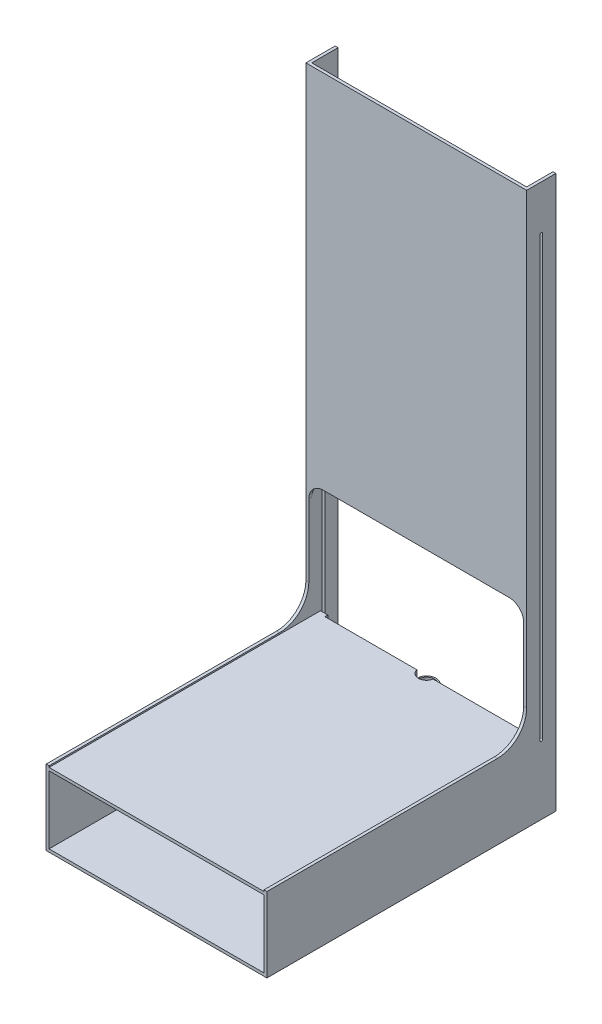
SolidWorks part; units mm, degrees
material "AISI 4340 Steel, annealed"
ref_plane "Front Plane" through (0, 0, 0) normal (0, 0, 1) x (1, 0, 0)
ref_plane "Top Plane" through (0, 0, 0) normal (0, 1, 0) x (1, 0, 0)
ref_plane "Right Plane" through (0, 0, 0) normal (1, 0, 0) x (0, 0, -1)
ref_plane "Right side of elevator platform" through (368, 0, 0) normal (1, 0, 0) x (0, 0, -1)
sketch "Sketch2" plane through (368, 0, 0) normal (1, 0, 0) x (0, 0, -1)
  line L0 (50, 236.5) -> (50, 1736.5) construction
  line L1 (45, 236.5) -> (45, 1736.5)
  line L2 (55, 236.5) -> (55, 1736.5)
  line L4 (0, 0) -> (100, 0)
  line L5 (0, 0) -> (0, 1800)
  line L6 (0, 1800) -> (100, 1800)
  line L7 (100, 0) -> (100, 1800)
  arc A0 (45, 236.5) -> (55, 236.5) centre (50, 236.5) ccw
  arc A1 (55, 1736.5) -> (45, 1736.5) centre (50, 1736.5) ccw
  point P2 (50, 986.5)
  dimension "D6" = 5
  dimension "D1" = 1800
  dimension "D2" = 100
  dimension "D3" = 50
  dimension "D4" = 236.5
  dimension "D5" = 63.5
extrude "Right side guide" add sketch "Sketch2" along normal blind 10
sketch "Sketch3" plane through (368, 0, 0) normal (-1, 0, 0) x (0, 0, 1)
  line L0 (0, 1800) -> (0, 0) construction
  line L1 (-100, 0) -> (0, 0)
  line L2 (-100, 0) -> (-100, 10)
  line L3 (-100, 10) -> (0, 10)
  line L4 (0, 0) -> (0, 10)
  dimension "D1" = 10
extrude "Bottom connection" add sketch "Sketch3" along normal blind 736
sketch "Sketch4" plane through (-368, 0, 0) normal (-1, 0, 0) x (0, 0, 1)
  line L0 (-55, 236.5) -> (-55, 1736.5) construction
  line L1 (-45, 1736.5) -> (-45, 236.5) construction
  line L2 (-55, 236.5) -> (-55, 1736.5)
  line L3 (-45, 1736.5) -> (-45, 236.5)
  line L4 (-100, 10) -> (0, 10)
  line L5 (0, 10) -> (0, 1800)
  line L6 (0, 1800) -> (-100, 1800)
  line L7 (-100, 1800) -> (-100, 10)
  line L9 (0, 10) -> (0, 1800)
  line L10 (0, 1800) -> (-100, 1800)
  line L11 (-100, 1800) -> (-100, 10)
  line L16 (-100, 10) -> (-100, 0)
  line L17 (-100, 0) -> (0, 0)
  line L18 (0, 0) -> (0, 10)
  line L19 (0, 10) -> (-100, 10)
  line L20 (-100, 10) -> (-100, 0)
  line L21 (-100, 0) -> (0, 0)
  line L22 (0, 0) -> (0, 10)
  arc A0 (-45, 1736.5) -> (-55, 1736.5) centre (-50, 1736.5) ccw construction
  arc A1 (-55, 236.5) -> (-45, 236.5) centre (-50, 236.5) ccw construction
  arc A2 (-45, 1736.5) -> (-55, 1736.5) centre (-50, 1736.5) ccw
  arc A3 (-55, 236.5) -> (-45, 236.5) centre (-50, 236.5) ccw
  dimension "D1" = 0
  dimension "D2" = 0
extrude "Left side guide" add sketch "Sketch4" along normal blind 10
sketch "Sketch5" plane through (0, 0, 0) normal (0, 0, 1) x (1, 0, 0)
  line L0 (-368, 10) -> (-368, 1800) construction
  line L1 (-368, 1800) -> (368, 1800)
  line L2 (-368, 1800) -> (-368, 653.8)
  line L3 (-368, 653.8) -> (368, 653.8)
  line L4 (368, 1800) -> (368, 653.8)
  line L5 (368, 1800) -> (368, 10) construction
  line L6 (378, 1800) -> (368, 1800) construction
  line L7 (-368, 10) -> (368, 10) construction
  dimension "D1" = 643.8
extrude "Structural webbing extrude" add sketch "Sketch5" against normal blind 10
sketch "Sketch6" plane through (0, 0, 0) normal (0, 0, 1) x (1, 0, 0)
  line L0 (-378, 251.5) -> (-378, 0)
  line L1 (-378, 0) -> (-378, 1800) construction
  line L2 (-378, 0) -> (378, 0)
  line L3 (378, 0) -> (378, 251.5)
  line L4 (378, 1800) -> (378, 0) construction
  line L5 (378, 251.5) -> (368, 251.5)
  line L6 (368, 653.8) -> (368, 10) construction
  line L7 (368, 251.5) -> (368, 10)
  line L8 (368, 10) -> (-368, 10)
  line L9 (-368, 10) -> (-368, 251.5)
  line L10 (-368, 10) -> (-368, 653.8) construction
  line L11 (-368, 251.5) -> (-378, 251.5)
  dimension "D1" = 241.5
extrude "Input roller holder extrude" add sketch "Sketch6" along normal blind 452.52
sketch "Sketch7" plane through (368, 0, 0) normal (-1, 0, 0) x (0, 0, 1)
  line L0 (0, 653.8) -> (0, 251.5) construction
  line L1 (452.52, 251.5) -> (-40, 251.5)
  line L2 (452.52, 251.5) -> (452.52, 241.5)
  line L3 (452.52, 241.5) -> (-40, 241.5)
  line L4 (-40, 251.5) -> (-40, 241.5)
  dimension "D1" = 40
  dimension "D2" = 10
extrude "Input roller platform" add sketch "Sketch7" along normal up to next
sketch "Sketch8" plane through (0, 251.5, 0) normal (0, 1, 0) x (1, 0, 0)
  line L1 (-378, -452.52) -> (-368, -452.52)
  line L2 (-378, -452.52) -> (-378, 0)
  line L3 (-378, 0) -> (-368, 0)
  line L4 (-368, -452.52) -> (-368, 0)
  line L5 (368, 0) -> (378, 0)
  line L6 (368, 0) -> (368, -452.52)
  line L7 (368, -452.52) -> (378, -452.52)
  line L8 (378, 0) -> (378, -452.52)
extrude "Siding outline" add sketch "Sketch8" along normal blind 5
sketch "Sketch9" plane through (0, 1800, 0) normal (0, 1, 0) x (1, 0, 0)
  line L8 (368, 100) -> (368, 10)
  line L9 (368, 10) -> (-368, 10)
  line L10 (-368, 10) -> (-368, 100)
  line L11 (-368, 100) -> (-378, 100)
  line L12 (-378, 100) -> (-378, 0)
  line L13 (-378, 0) -> (378, 0)
  line L14 (378, 0) -> (378, 100)
  line L15 (378, 100) -> (368, 100)
  line L16 (368, 100) -> (368, 10)
  line L17 (368, 10) -> (-368, 10)
  line L18 (-368, 10) -> (-368, 100)
  line L19 (-368, 100) -> (-378, 100)
  line L20 (-378, 100) -> (-378, 0)
  line L21 (-378, 0) -> (378, 0)
  line L22 (378, 0) -> (378, 100)
  line L23 (378, 100) -> (368, 100)
  dimension "D1" = 0
extrude "Lip to prevent box from falling out" add sketch "Sketch9" along normal blind 91.5
fillet "Vertical section fillets" radius 100 2 edges at (373, 256.5, 0) (-373, 256.5, 0)
fillet "Smaller fillets" radius 50 2 edges at (368, 653.8, -5) (-368, 653.8, -5)
sketch "Sketch11" plane through (0, 0, -40) normal (0, 0, -1) x (-1, 0, 0)
  line L0 (368, 251.5) -> (-368, 251.5) construction
  line L1 (-343, 251.5) -> (343, 251.5)
  line L2 (-343, 251.5) -> (-343, 241.5)
  line L3 (-343, 241.5) -> (343, 241.5)
  line L4 (343, 251.5) -> (343, 241.5)
  line L5 (368, 241.5) -> (-368, 241.5) construction
  line L6 (-368, 251.5) -> (-368, 241.5) construction
  line L7 (368, 251.5) -> (368, 241.5) construction
  dimension "D1" = 25
  dimension "D2" = 25
extrude "Gate spacing cut" cut sketch "Sketch11" against normal blind 10
sketch "Sketch12" plane through (-368, 0, 0) normal (1, 0, 0) x (0, 0, -1)
  line L1 (45, 221.5) -> (40, 221.5)
  line L2 (45, 221.5) -> (45, 10)
  line L3 (45, 10) -> (40, 10)
  line L4 (40, 221.5) -> (40, 10)
  line L5 (100, 1891.5) -> (100, 10) construction
  line L6 (45, 236.5) -> (45, 1736.5) construction
  line L7 (-452.52, 10) -> (100, 10) construction
  line L8 (40, 241.5) -> (-452.52, 241.5) construction
  line L9 (30, 241.5) -> (25, 241.5)
  line L10 (30, 241.5) -> (30, 10)
  line L11 (30, 10) -> (25, 10)
  line L12 (25, 241.5) -> (25, 10)
  dimension "D1" = 60
  dimension "D2" = 20
  dimension "D3" = 5
extrude "Gate guide rails" add sketch "Sketch12" along normal up to next
sketch "Sketch13" plane through (0, 0, -45) normal (0, 0, -1) x (-1, 0, 0)
  line L0 (-368, 221.5) -> (368, 221.5) construction
  line L1 (-328, 221.5) -> (328, 221.5)
  line L2 (-328, 221.5) -> (-328, 10)
  line L3 (-328, 10) -> (328, 10)
  line L4 (328, 221.5) -> (328, 10)
  line L5 (368, 10) -> (-368, 10) construction
  line L6 (-368, 10) -> (-368, 1891.5) construction
  point P8 (0, 221.5)
  dimension "D1" = 40
extrude "Gate rod connection cutout" cut sketch "Sketch13" against normal through all
sketch "Sketch14" plane through (0, 10, 0) normal (0, 1, 0) x (1, 0, 0)
  line L0 (328, 45) -> (-328, 25) construction
  circle A0 centre (0, 35) radius 28
  circle A1 centre (0, 35) radius 33
  point P7 (0, 35)
  dimension "D1" = 56
  dimension "D2" = 5
extrude "Spring cup" add sketch "Sketch14" along normal blind 75
sketch "Sketch15" plane through (0, 85, 0) normal (0, 1, 0) x (1, 0, 0)
  line L0 (368, 30) -> (328, 30) construction
  line L1 (32.619, 30) -> (27.55, 30)
  line L3 (32.619, 40) -> (27.55, 40)
  line L5 (-27.55, 40) -> (-32.619, 40)
  line L6 (-27.55, 30) -> (-32.619, 30)
  circle A0 centre (0, 35) radius 28 construction
  arc A1 (27.55, 40) -> (-27.55, 40) centre (0, 35) ccw
  circle A2 centre (0, 35) radius 33 construction
  arc A3 (32.619, 40) -> (-32.619, 40) centre (0, 35) ccw
  arc A4 (-27.55, 30) -> (27.55, 30) centre (0, 35) ccw
  arc A5 (-32.619, 30) -> (32.619, 30) centre (0, 35) ccw
extrude "Spring container extension" add sketch "Sketch15" along normal up to surface (136.5 mm away) up to face at (0, 221.5, -27.5)
sketch "Sketch16" plane through (0, 221.5, 0) normal (0, 1, 0) x (1, 0, 0)
  circle A0 centre (0, 35) radius 28
  arc A1 (27.55, 40) -> (-27.55, 40) centre (0, 35) ccw construction
extrude "Spring hole (can't insert spring without this)" cut sketch "Sketch16" along normal up to surface (30 mm away) up to face at (0, 251.5, 85.63)
sketch "Sketch17" plane through (0, 221.5, 0) normal (0, 1, 0) x (1, 0, 0)
  line L2 (-26.1534, 25) -> (-31.4484, 25)
  line L3 (31.4484, 25) -> (26.1534, 25)
  line L4 (-26.1534, 25) -> (-31.4484, 25)
  line L5 (31.4484, 25) -> (26.1534, 25)
  arc A2 (-31.4484, 25) -> (31.4484, 25) centre (0, 35) ccw
  arc A3 (-26.1534, 25) -> (26.1534, 25) centre (0, 35) ccw
  arc A4 (-31.4484, 25) -> (31.4484, 25) centre (0, 35) ccw
  arc A5 (-26.1534, 25) -> (26.1534, 25) centre (0, 35) ccw
  dimension "D1" = 0
extrude "Container extension to meet with conveyor plate" add sketch "Sketch17" along normal up to next
fillet "Spring holder fillets" radius 10 4 edges at (0, 10, -68) (-31.4484, 231.5, -25) (31.4484, 231.5, -25) (0, 241.5, -2)
sketch "Sketch18" plane through (0, 0, 452.52) normal (0, 0, 1) x (1, 0, 0)
  line L0 (368, 10) -> (368, 241.5) construction
  line L1 (-368, 241.5) -> (-368, 10) construction
  line L2 (368, 10) -> (368, 241.5)
  line L3 (-368, 241.5) -> (-368, 10)
  line L4 (-368, 241.5) -> (368, 241.5)
  line L5 (368, 10) -> (-368, 10)
  line L8 (378, 0) -> (378, 256.5)
  line L9 (378, 256.5) -> (368, 256.5)
  line L10 (368, 256.5) -> (368, 251.5)
  line L11 (368, 251.5) -> (-368, 251.5)
  line L12 (-368, 251.5) -> (-368, 256.5)
  line L13 (-368, 256.5) -> (-378, 256.5)
  line L14 (-378, 256.5) -> (-378, 0)
  line L15 (-378, 0) -> (378, 0)
  line L16 (378, 0) -> (378, 256.5)
  line L17 (378, 256.5) -> (368, 256.5)
  line L18 (368, 256.5) -> (368, 251.5)
  line L19 (368, 251.5) -> (-368, 251.5)
  line L20 (-368, 251.5) -> (-368, 256.5)
  line L21 (-368, 256.5) -> (-378, 256.5)
  line L22 (-378, 256.5) -> (-378, 0)
  line L23 (-378, 0) -> (378, 0)
  dimension "D1" = 0
extrude "Extension to fit with sorter loop exit stuff" add sketch "Sketch18" along normal blind 437
